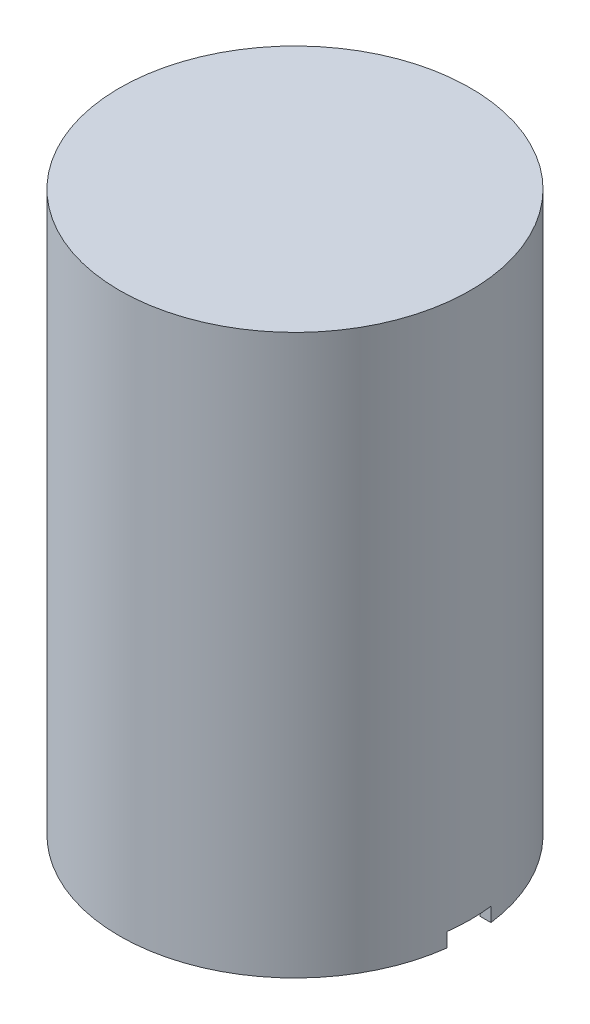
SolidWorks part; units mm, degrees
material "ABS"
ref_plane "Front Plane" through (0, 0, 0) normal (0, 0, 1) x (1, 0, 0)
ref_plane "Top Plane" through (0, 0, 0) normal (0, 1, 0) x (1, 0, 0)
ref_plane "Right Plane" through (0, 0, 0) normal (1, 0, 0) x (0, 0, -1)
sketch "Sketch1" plane through (0, 0, 0) normal (0, 1, 0) x (1, 0, 0)
  circle A1 centre (0, 0) radius 32
  dimension "D2" = 64
extrude "Boss-Extrude1" add sketch "Sketch1" along normal blind 100 contours A1
sketch "Sketch2" plane through (0, 0, 0) normal (0, -1, 0) x (1, 0, 0)
  circle A0 centre (0, 0) radius 30.025
  dimension "D1" = 60.05
extrude "Cut-Extrude1" cut sketch "Sketch2" against normal blind 59 contours A0
sketch "Sketch3" plane through (0, 100, 0) normal (0, 1, 0) x (1, 0, 0)
  circle A0 centre (0, 0) radius 32
extrude "Boss-Extrude2" add sketch "Sketch3" along normal blind 2
sketch "Sketch4" plane through (0, 0, 0) normal (0, 0, 1) x (1, 0, 0)
  line L1 (34.8707, -3.2533) -> (-35.2648, -3.2533)
  line L2 (34.8707, -3.2533) -> (34.8707, 2.5906)
  line L3 (34.8707, 2.5906) -> (-35.2648, 2.5906)
  line L4 (-35.2648, -3.2533) -> (-35.2648, 2.5906)
extrude "Cut-Extrude2" cut sketch "Sketch4" against normal blind 4 and the other way blind 4
